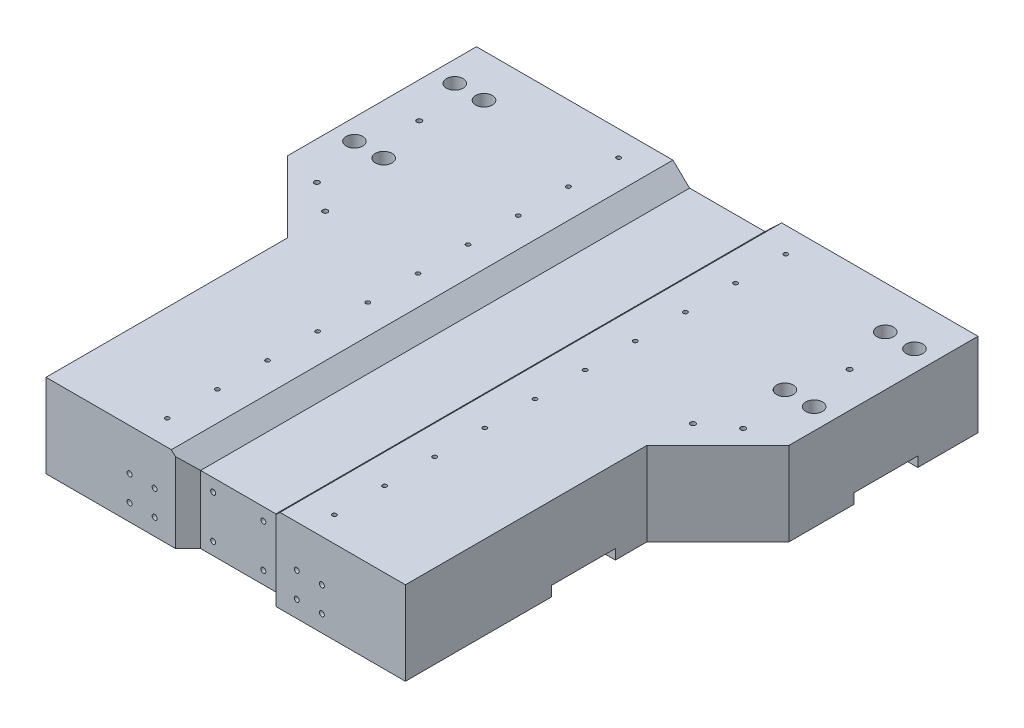
SolidWorks part; units mm, degrees
ref_plane "Front Plane" through (0, 0, 0) normal (0, 0, 1) x (1, 0, 0)
ref_plane "Top Plane" through (0, 0, 0) normal (0, 1, 0) x (1, 0, 0)
ref_plane "Right Plane" through (0, 0, 0) normal (1, 0, 0) x (0, 0, -1)
sketch "Sketch1" plane through (0, 0, 0) normal (0, 1, 0) x (1, 0, 0)
  line L1 (-300, 300) -> (300, 300)
  line L2 (-300, 300) -> (-300, -300)
  line L3 (-300, -300) -> (300, -300)
  line L4 (300, 300) -> (300, -300)
  line L5 (0, -300) -> (0, 300) construction
  line L6 (-300, 0) -> (300, 0) construction
  point P0 (0, 0)
  dimension "D1" = 600
extrude "Boss-Extrude1" add sketch "Sketch1" along normal blind 100
sketch "Sketch2" plane through (0, 100, 0) normal (0, 1, 0) x (1, 0, 0)
  line L0 (-300, -300) -> (-220, -300)
  line L9 (-300, -300) -> (300, -300) construction
  line L11 (300, -300) -> (220, -300)
  line L13 (-300, 300) -> (-300, -300) construction
  line L15 (-300, -300) -> (-300, 60)
  line L16 (300, -300) -> (300, 60)
  line L38 (-300, 60) -> (-300, 74)
  line L41 (300, 60) -> (300, 74)
  line L45 (-220, 74) -> (-300, 74)
  line L48 (220, 74) -> (300, 74)
  line L49 (-220, 74) -> (-215, 74)
  line L50 (-215, 74) -> (-215, -300)
  line L51 (-215, -300) -> (-220, -300)
  line L52 (220, 74) -> (215, 74)
  line L53 (215, 74) -> (215, -300)
  line L54 (215, -300) -> (220, -300)
extrude "Cut-Extrude1" cut sketch "Sketch2" against normal through all
chamfer "Chamfer5" distance 85 angle 45 2 edges at (-215, 50, -74) (215, 50, -74)
sketch "Sketch3" plane through (0, 0, 300) normal (0, 0, 1) x (1, 0, 0)
  line L0 (-35, 81) -> (-45, 81)
  line L2 (35, 81) -> (45, 81)
  line L4 (0, 81) -> (35, 81)
  line L8 (0, 81) -> (-35, 81)
  line L10 (-45, 100) -> (45, 100)
  line L13 (-215, 100) -> (215, 100) construction
  line L14 (-65, 100) -> (-45, 100)
  line L17 (45, 100) -> (65, 100)
  line L22 (-45, 81) -> (-65, 100)
  line L23 (45, 81) -> (65, 100)
extrude "Cut-Extrude2" cut sketch "Sketch3" against normal through all
sketch "Sketch9" plane through (0, 100, 0) normal (0, 1, 0) x (1, 0, 0)
  circle A0 centre (275, 129) radius 10
  circle A1 centre (240, 129) radius 10
  circle A3 centre (240, 249) radius 10
  circle A5 centre (275, 249) radius 10
  circle A6 centre (-275, 129) radius 10
  circle A7 centre (-240, 249) radius 10
  circle A8 centre (-275, 249) radius 10
  circle A11 centre (-240, 129) radius 10
  circle A12 centre (240, 189) radius 10 [skipped]
  circle A13 centre (275, 189) radius 10 [skipped]
  dimension "D1" = 2
  dimension "D2" = 3
extrude "Cut-Extrude5" cut sketch "Sketch9" against normal through all
sketch "Sketch12" plane through (0, 100, 0) normal (0, 1, 0) x (1, 0, 0)
  circle A40 centre (-100, -270) radius 2.5
  circle A41 centre (100, -270) radius 2.5
  circle A42 centre (100, -210) radius 2.5
  circle A43 centre (100, -150) radius 2.5
  circle A44 centre (100, -90) radius 2.5
  circle A45 centre (100, -30) radius 2.5
  circle A46 centre (100, 30) radius 2.5
  circle A47 centre (100, 90) radius 2.5
  circle A48 centre (100, 150) radius 2.5
  circle A49 centre (100, 210) radius 2.5
  circle A50 centre (100, 270) radius 2.5
  circle A61 centre (-100, -210) radius 2.5
  circle A62 centre (-100, -150) radius 2.5
  circle A63 centre (-100, -90) radius 2.5
  circle A64 centre (-100, -30) radius 2.5
  circle A65 centre (-100, 30) radius 2.5
  circle A66 centre (-100, 90) radius 2.5
  circle A67 centre (-100, 150) radius 2.5
  circle A68 centre (-100, 210) radius 2.5
  circle A69 centre (-100, 270) radius 2.5
  dimension "D1" = 2
  dimension "D2" = 10
extrude "Cut-Extrude7" cut sketch "Sketch12" against normal blind 30
sketch "Sketch14" plane through (0, 81, 0) normal (0, 1, 0) x (1, 0, 0)
  line L5 (-45, -300) -> (45, -300)
  line L6 (-45, -300) -> (-45, -285)
  line L11 (45, -285) -> (45, -300)
  line L15 (-45, -285) -> (45, -285)
extrude "Cut-Extrude8" cut sketch "Sketch14" against normal through all
chamfer "Chamfer3" distance 15 angle 45 2 edges at (45, 40.5, 300) (-45, 40.5, 300)
sketch "Sketch15" plane through (-300, 0, 0) normal (-1, 0, 0) x (0, 0, 1)
  line L0 (125, -0.7) -> (125, 12) construction
  line L1 (125, 12) -> (48.8, 12) construction
  line L2 (48.8, 12) -> (48.8, -0.7) construction
  line L3 (48.8, -0.7) -> (125, -0.7) construction
  line L4 (-228, 12) -> (-228, -0.7) construction
  line L5 (-228, -0.7) -> (-151.8, -0.7) construction
  line L6 (-151.8, -0.7) -> (-151.8, 12) construction
  line L7 (-151.8, 12) -> (-228, 12) construction
  line L8 (125, -0.7) -> (125, 12)
  line L9 (125, 12) -> (48.8, 12)
  line L10 (48.8, 12) -> (48.8, -0.7)
  line L11 (48.8, -0.7) -> (125, -0.7)
  line L12 (-228, 12) -> (-228, -0.7)
  line L13 (-228, -0.7) -> (-151.8, -0.7)
  line L14 (-151.8, -0.7) -> (-151.8, 12)
  line L15 (-151.8, 12) -> (-228, 12)
extrude "Cut-Extrude9" cut sketch "Sketch15" against normal through all
sketch "Sketch22" plane through (0, 0, -300) normal (0, 0, -1) x (-1, 0, 0)
  line L0 (-45, 81) -> (-45, 0)
  line L1 (-300, 0) -> (300, 0) construction
  line L2 (-45, 0) -> (45, 0)
  line L3 (45, 0) -> (45, 81)
  line L4 (45, 81) -> (-45, 81)
sketch "Sketch17" plane through (0, 0, 285) normal (0, 0, 1) x (1, 0, 0)
  line L8 (30, 66) -> (-30, 66)
  line L9 (-30, 66) -> (-30, 15)
  line L10 (-30, 15) -> (30, 15)
  line L11 (30, 15) -> (30, 66)
  line L12 (30, 66) -> (-30, 66)
  line L13 (-30, 66) -> (-30, 15)
  line L14 (-30, 15) -> (30, 15)
  line L15 (30, 15) -> (30, 66)
  dimension "D1" = 15
sketch "Sketch19" plane through (0, 0, -300) normal (0, 0, -1) x (-1, 0, 0)
  line L0 (30, 66) -> (30, 15) construction
  line L1 (30, 15) -> (-30, 15) construction
  line L2 (-30, 15) -> (-30, 66) construction
  line L3 (-30, 66) -> (30, 66) construction
  line L4 (30, 66) -> (30, 15)
  line L5 (30, 15) -> (-30, 15)
  line L6 (-30, 15) -> (-30, 66)
  line L7 (-30, 66) -> (30, 66)
sketch "Sketch20" plane through (0, 0, 300) normal (0, 0, 1) x (1, 0, 0)
  line L2 (85, 100) -> (85, 50)
  line L3 (-85, 0) -> (-85, 20)
  line L4 (-215, 100) -> (-65, 100) construction
  line L5 (-85, 100) -> (-85, 50)
  line L6 (115, 100) -> (115, 50)
  line L7 (-115, 100) -> (-115, 50)
  line L8 (0, 34.1921) -> (0, 91.6213)
  line L9 (-215, 0) -> (-60, 0) construction
  line L10 (-115, 0) -> (-115, 20)
  line L11 (85, 0) -> (85, 20)
  line L12 (115, 0) -> (115, 20)
sketch "Sketch21" plane through (0, 0, -300) normal (0, 0, -1) x (-1, 0, 0)
  line L4 (-115, 100) -> (-115, 80)
  line L5 (-85, 100) -> (-85, 80)
  line L6 (85, 100) -> (85, 80)
  line L7 (115, 100) -> (115, 80)
  line L8 (115, 0) -> (115, 20) construction
  line L9 (85, 0) -> (85, 20) construction
  line L10 (-85, 0) -> (-85, 20) construction
  line L11 (-115, 0) -> (-115, 20) construction
  line L12 (115, 0) -> (115, 20)
  line L13 (85, 0) -> (85, 20)
  line L14 (-85, 0) -> (-85, 20)
  line L15 (-115, 0) -> (-115, 20)
hole_wizard "Ø6.0mm Dowel Hole1" positions "3DSketch2" profile "Sketch18" hole size "Ø6.0" standard "ANSI Metric"
sketch3d "3DSketch2"
  point P0 (-30, 66, 285)
  point P3 (30, 66, 285)
  point P6 (30, 15, 285)
  point P9 (-30, 15, 285)
  point P13 (30, 66, -300)
  point P16 (-30, 66, -300)
  point P19 (-30, 15, -300)
  point P22 (30, 15, -300)
  point P26 (-85, 50, 300)
  point P29 (-115, 50, 300)
  point P32 (85, 50, 300)
  point P35 (115, 50, 300)
  point P38 (-115, 80, -300)
  point P41 (-85, 80, -300)
  point P44 (85, 80, -300)
  point P47 (115, 80, -300)
  point P50 (-115, 20, 300)
  point P53 (-85, 20, 300)
  point P56 (85, 20, 300)
  point P59 (115, 20, 300)
  point P62 (-115, 20, -300)
  point P65 (-85, 20, -300)
  point P68 (85, 20, -300)
  point P71 (115, 20, -300)
sketch "Sketch18" plane through (-30, 66, 285) normal (1, 0, 0) x (0, -1, 0)
  line L0 (0, 0) -> (0, 31.8026)
  line L1 (0, 31.8026) -> (3, 30)
  line L2 (3, 30) -> (3, 0)
  line L5 (3, 0) -> (0, 0)
  line L10 (0, 31.8026) -> (-3, 30) construction
  line L11 (0, -6.35) -> (0, 107.95) construction
  dimension "Hole Dia." = 6
  dimension "Hole Depth" = 30
  dimension "Drill Angle" = 118
sketch "Sketch23" plane through (0, 100, 0) normal (0, 1, 0) x (1, 0, 0)
  circle A0 centre (-257.5, 189) radius 3
  circle A1 centre (257.5, 189) radius 3
extrude "Cut-Extrude10" cut sketch "Sketch23" against normal through all
sketch "Sketch24" plane through (0, 100, 0) normal (0, 1, 0) x (1, 0, 0)
  line L0 (210, 74) -> (300, 74) construction
  line L1 (210, 74) -> (300, 74)
  line L2 (210, 74) -> (210, 4)
  line L3 (210, 39) -> (220, 39)
  line L4 (255, 74) -> (255, 64)
  line L5 (0, 0) -> (0, -82.778)
  circle A0 centre (255, 64) radius 3
  circle A1 centre (220, 39) radius 3
  circle A2 centre (-220, 39) radius 3
  circle A3 centre (-255, 64) radius 3
extrude "Cut-Extrude11" cut sketch "Sketch24" against normal blind 20 contours A3 | A2 | A0 | A1
